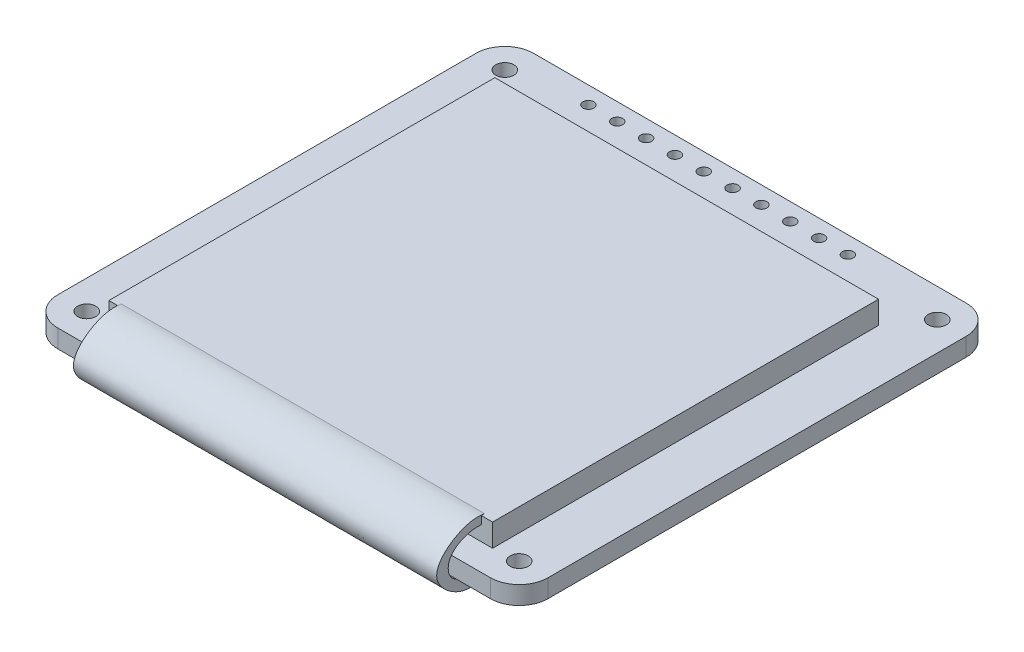
SolidWorks part; units mm, degrees
ref_plane "Front Plane" through (0, 0, 0) normal (0, 0, 1) x (1, 0, 0)
ref_plane "Top Plane" through (0, 0, 0) normal (0, 1, 0) x (1, 0, 0)
ref_plane "Right Plane" through (0, 0, 0) normal (1, 0, 0) x (0, 0, -1)
sketch "Sketch1" plane through (0, 0, 0) normal (0, 1, 0) x (1, 0, 0)
  line L0 (0, 39.37) -> (0, 2.54)
  line L1 (2.54, 0) -> (40.64, 0)
  line L2 (43.18, 2.54) -> (43.18, 39.37)
  line L3 (40.64, 41.91) -> (2.54, 41.91)
  arc A0 (0, 2.54) -> (2.54, 0) centre (2.54, 2.54) ccw
  arc A1 (40.64, 0) -> (43.18, 2.54) centre (40.64, 2.54) ccw
  arc A2 (43.18, 39.37) -> (40.64, 41.91) centre (40.64, 39.37) ccw
  arc A3 (2.54, 41.91) -> (0, 39.37) centre (2.54, 39.37) ccw
  circle A4 centre (31.75, 40.386) radius 0.4826
  circle A5 centre (31.75, 40.386) radius 0.4826
  circle A6 centre (29.21, 40.386) radius 0.4826
  circle A7 centre (29.21, 40.386) radius 0.4826
  circle A8 centre (26.67, 40.386) radius 0.4826
  circle A9 centre (26.67, 40.386) radius 0.4826
  circle A10 centre (24.13, 40.386) radius 0.4826
  circle A11 centre (24.13, 40.386) radius 0.4826
  circle A12 centre (21.59, 40.386) radius 0.4826
  circle A13 centre (21.59, 40.386) radius 0.4826
  circle A14 centre (19.05, 40.386) radius 0.4826
  circle A15 centre (19.05, 40.386) radius 0.4826
  circle A16 centre (16.51, 40.386) radius 0.4826
  circle A17 centre (16.51, 40.386) radius 0.4826
  circle A18 centre (13.97, 40.386) radius 0.4826
  circle A19 centre (13.97, 40.386) radius 0.4826
  circle A20 centre (11.43, 40.386) radius 0.4826
  circle A21 centre (11.43, 40.386) radius 0.4826
  circle A22 centre (8.89, 40.386) radius 0.4826
  circle A23 centre (8.89, 40.386) radius 0.4826
  circle A24 centre (2.54, 2.54) radius 0.8
  circle A25 centre (2.54, 2.54) radius 0.8
  circle A26 centre (40.64, 2.54) radius 0.8
  circle A27 centre (40.64, 2.54) radius 0.8
  circle A28 centre (40.64, 39.37) radius 0.8
  circle A29 centre (40.64, 39.37) radius 0.8
  circle A30 centre (2.54, 39.37) radius 0.8
  circle A31 centre (2.54, 39.37) radius 0.8
extrude "Boss-Extrude1" add sketch "Sketch1" along normal blind 1.6 contours L3 A3 L0 A0 L1 A1 L2 A2 A30 A28 A26 A24 A22 A20 A18 A16 A14 A12 A10 A8 A6 A4 region at (21.5952, 0, -20.8755)
sketch "Sketch2" plane through (0, 1.6, 0) normal (0, 1, 0) x (1, 0, 0)
  line L0 (0, 39.37) -> (0, 2.54) construction
  line L1 (4.69, 36.3438) -> (38.49, 36.3438)
  line L2 (4.69, 36.3438) -> (4.69, 2.3438)
  line L3 (4.69, 2.3438) -> (38.49, 2.3438)
  line L4 (38.49, 36.3438) -> (38.49, 2.3438)
  line L5 (43.18, 2.54) -> (43.18, 39.37) construction
  dimension "D1" = 33.8
  dimension "D2" = 34
  dimension "D3" = 4.69
  dimension "D4" = 4.69
extrude "Boss-Extrude2" add sketch "Sketch2" along normal blind 2
sketch "Sketch3" plane through (0, 0, 0) normal (1, 0, 0) x (0, 0, -1)
  spline S0 degree 3 poles (8.2816, -0.2295) (4.1539, 3.3516) (1.0034, 4.0569) (-2.8961, 1.1671) (0.1, -1.4379) (2.9832, -1.4241) (8.2816, -0.2295) (4.1539, 3.3516) (1.0034, 4.0569) knots -0.504023 -0.428158 -0.185343 0 0.142118 0.339134 0.495977 0.571842 0.814657 1 1.142118 1.339134 1.495977 only from (3.9702, 3.1053) to (3.9702, 3.1053)
  spline S1 degree 3 poles (5.1576, 1.2954) (3.6929, 2.6724) (1.536, 3.293) (-0.8599, 1.8627) (-0.4616, 0.1711) (1.129, -0.6658) (3.1681, -0.4896) (4.995, 0.0056) (5.1576, 1.2954) (3.6929, 2.6724) (1.536, 3.293) knots -0.252278 -0.209355 -0.084678 0 0.200569 0.386571 0.476144 0.515166 0.747722 0.790645 0.915322 1 1.200569 1.386571 1.476144 only from (4.0818, 2.2318) to (4.0818, 2.2318)
extrude "Boss-Extrude3" add sketch "Sketch3" along normal blind 32 from offset 5.5
